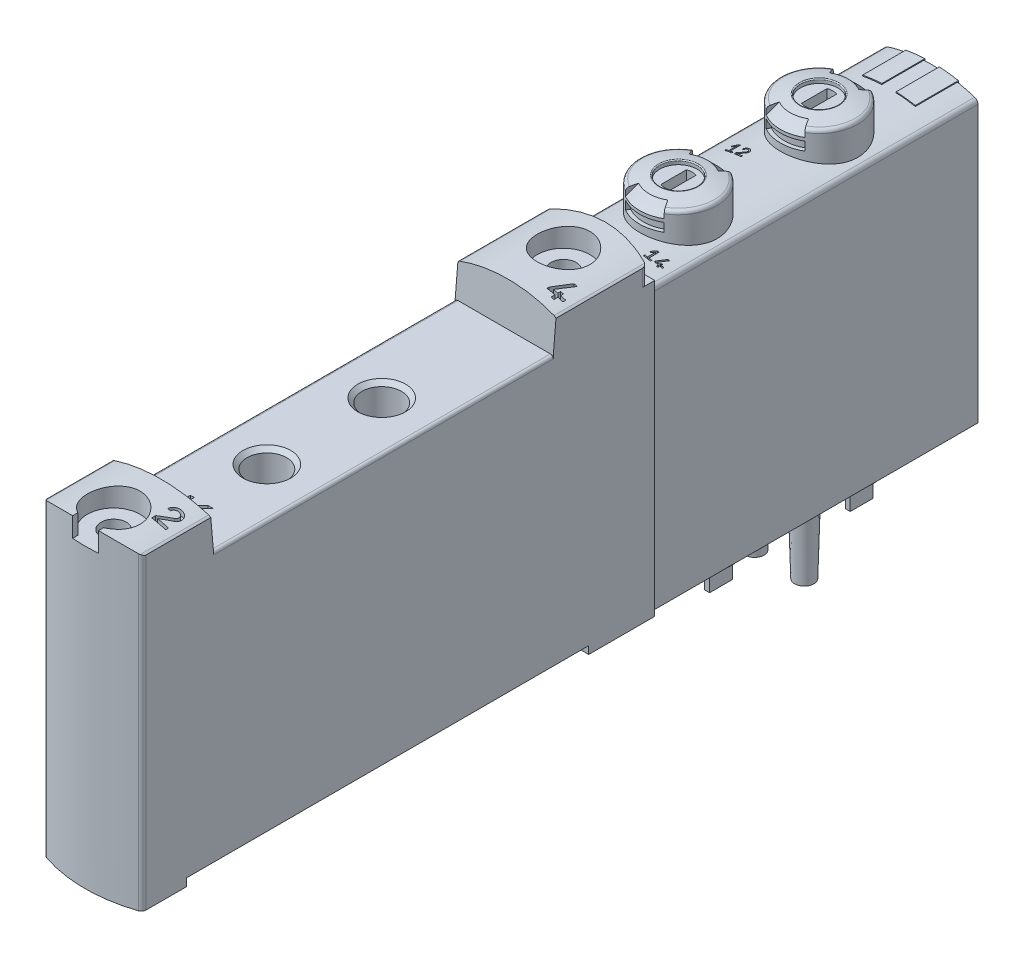
SolidWorks part; units mm, degrees
ref_plane "Front Plane" through (0, 0, 0) normal (0, 0, 1) x (1, 0, 0)
ref_plane "Top Plane" through (0, 0, 0) normal (0, 1, 0) x (1, 0, 0)
ref_plane "Right Plane" through (0, 0, 0) normal (1, 0, 0) x (0, 0, -1)
ref_plane "Plane1" through (0, 0, -23.2) normal (0, 0, 1) x (1, 0, 0)
sketch "Sketch1" plane through (0, 0, -23.2) normal (0, 0, 1) x (1, 0, 0)
  line L0 (-4.9, 29.2163) -> (-4.9, 0)
  line L1 (-4.9, 0) -> (4.9, 0)
  line L2 (4.9, 0) -> (4.9, 29.2163)
  arc A0 (4.9, 29.2163) -> (4.5517, 29.6927) centre (4.4, 29.2163) ccw
  arc A1 (4.5517, 29.6927) -> (-4.5517, 29.6927) centre (0, 15.4) ccw
  arc A2 (-4.5517, 29.6927) -> (-4.9, 29.2163) centre (-4.4, 29.2163) ccw
extrude "Boss-Extrude1" add sketch "Sketch1" along normal blind 34
ref_plane "Plane2" through (0, 0, 0) normal (1, 0, 0) x (0, 0, -1)
sketch "Sketch2" plane through (0, 0, 0) normal (1, 0, 0) x (0, 0, -1)
  line L0 (-10.88, 0.4) -> (-10.88, 0)
  line L1 (-10.88, 0) -> (23.22, 0)
  line L2 (23.22, 0) -> (23.22, 0.4)
  line L3 (23.22, 0.4) -> (-10.88, 0.4)
extrude "Cut-Extrude1" cut sketch "Sketch2" against normal blind 6 and the other way blind 6
ref_plane "Plane3" through (0, 0, 0) normal (0, 1, 0) x (1, 0, 0)
sketch "Sketch3" plane through (0, 0, 0) normal (0, 1, 0) x (1, 0, 0)
  line L0 (-3.15, 2.4653) -> (-3.15, -2.4653)
  line L1 (3.15, -2.4653) -> (3.15, 2.4653)
  arc A0 (-3.15, -2.4653) -> (3.15, -2.4653) centre (0, 0) ccw
  arc A1 (3.15, 2.4653) -> (-3.15, 2.4653) centre (0, 0) ccw
extrude "Cut-Extrude2" cut sketch "Sketch3" along normal blind 1.9
ref_plane "Plane4" through (0, 0, 0) normal (0, 1, 0) x (1, 0, 0)
sketch "Sketch4" plane through (0, 0, 0) normal (0, 1, 0) x (1, 0, 0)
  line L0 (-3.15, 17.1653) -> (-3.15, 12.2347)
  line L1 (3.15, 12.2347) -> (3.15, 17.1653)
  arc A0 (-3.15, 12.2347) -> (3.15, 12.2347) centre (0, 14.7) ccw
  arc A1 (3.15, 17.1653) -> (-3.15, 17.1653) centre (0, 14.7) ccw
extrude "Cut-Extrude3" cut sketch "Sketch4" along normal blind 1.9
ref_plane "Plane5" through (0, 0, 0) normal (1, 0, 0) x (0, 0, -1)
sketch "Sketch5" plane through (0, 0, 0) normal (1, 0, 0) x (0, 0, -1)
  line L0 (0, 2.1) -> (3.05, 2.1)
  line L1 (3.05, 2.1) -> (3.05, 1.1)
  line L2 (3.05, 1.1) -> (2.25, 1.1)
  line L3 (2.25, 1.1) -> (2.25, -1.4)
  line L4 (2.25, -1.4) -> (2.65, -1.4)
  line L5 (2.65, -1.4) -> (2.65, -1.72)
  line L6 (2.65, -1.72) -> (2.4306, -2.1)
  line L7 (2.4306, -2.1) -> (0, -2.1)
  line L8 (0, -2.1) -> (0, 2.1)
  line L9 (0, -2.1) -> (0, 2.1) construction
revolve "Revolve1" add sketch "Sketch5" angle 360 about L9 reverse direction yes
ref_plane "Plane6" through (0, 0, 0) normal (1, 0, 0) x (0, 0, -1)
sketch "Sketch6" plane through (0, 0, 0) normal (1, 0, 0) x (0, 0, -1)
  line L0 (14.7, 2.1) -> (17.75, 2.1)
  line L1 (17.75, 2.1) -> (17.75, 1.1)
  line L2 (17.75, 1.1) -> (16.95, 1.1)
  line L3 (16.95, 1.1) -> (16.95, -1.4)
  line L4 (16.95, -1.4) -> (17.35, -1.4)
  line L5 (17.35, -1.4) -> (17.35, -1.72)
  line L6 (17.35, -1.72) -> (17.1306, -2.1)
  line L7 (17.1306, -2.1) -> (14.7, -2.1)
  line L8 (14.7, -2.1) -> (14.7, 2.1)
  line L9 (14.7, -2.1) -> (14.7, 2.1) construction
revolve "Revolve2" add sketch "Sketch6" angle 360 about L9 reverse direction yes
ref_plane "Plane7" through (0, 0, -7.35) normal (0, 0, 1) x (1, 0, 0)
sketch "Sketch7" plane through (0, 0, -7.35) normal (0, 0, 1) x (1, 0, 0)
  line L0 (2.6, 0.4) -> (3.8, 0.4)
  line L1 (3.8, 0.4) -> (3.6, -6.9)
  line L2 (2.6, -7.0623) -> (2.6, 0.4)
  line L3 (2.6, -7.0623) -> (2.6, 0.4) construction
  arc A0 (3.6, -6.9) -> (2.6, -7.0623) centre (2.6, -3.9) cw
revolve "Revolve3" add sketch "Sketch7" angle 360 about L3 reverse direction yes
ref_plane "Plane8" through (0, 0, -7.35) normal (0, 0, 1) x (1, 0, 0)
sketch "Sketch8" plane through (0, 0, -7.35) normal (0, 0, 1) x (1, 0, 0)
  line L0 (-2.6, 0.4) -> (-1.4, 0.4)
  line L1 (-1.4, 0.4) -> (-1.6, -6.9)
  line L2 (-2.6, -7.0623) -> (-2.6, 0.4)
  line L3 (-2.6, -7.0623) -> (-2.6, 0.4) construction
  arc A0 (-1.6, -6.9) -> (-2.6, -7.0623) centre (-2.6, -3.9) cw
revolve "Revolve4" add sketch "Sketch8" angle 360 about L3 reverse direction yes
ref_plane "Plane9" through (0, -2.1, 0) normal (0, -1, 0) x (-1, 0, 0)
sketch "Sketch9" plane through (0, -2.1, 0) normal (0, -1, 0) x (-1, 0, 0)
  line L0 (-1.25, -1.2) -> (-0.75, -1.2)
  line L1 (-0.75, -1.2) -> (-0.75, 1.2)
  line L2 (-0.75, 1.2) -> (-1.25, 1.2)
  line L3 (-1.25, 1.2) -> (-1.25, -1.2)
extrude "Boss-Extrude2" add sketch "Sketch9" along normal blind 2.5
ref_plane "Plane10" through (0, -2.1, 0) normal (0, -1, 0) x (-1, 0, 0)
sketch "Sketch10" plane through (0, -2.1, 0) normal (0, -1, 0) x (-1, 0, 0)
  line L0 (0.75, -1.2) -> (1.25, -1.2)
  line L1 (1.25, -1.2) -> (1.25, 1.2)
  line L2 (1.25, 1.2) -> (0.75, 1.2)
  line L3 (0.75, 1.2) -> (0.75, -1.2)
extrude "Boss-Extrude3" add sketch "Sketch10" along normal blind 2.5
ref_plane "Plane11" through (0, -2.1, 0) normal (0, -1, 0) x (-1, 0, 0)
sketch "Sketch11" plane through (0, -2.1, 0) normal (0, -1, 0) x (-1, 0, 0)
  line L0 (-1.25, 13.5) -> (-0.75, 13.5)
  line L1 (-0.75, 13.5) -> (-0.75, 15.9)
  line L2 (-0.75, 15.9) -> (-1.25, 15.9)
  line L3 (-1.25, 15.9) -> (-1.25, 13.5)
extrude "Boss-Extrude4" add sketch "Sketch11" along normal blind 2.5
ref_plane "Plane12" through (0, -2.1, 0) normal (0, -1, 0) x (-1, 0, 0)
sketch "Sketch12" plane through (0, -2.1, 0) normal (0, -1, 0) x (-1, 0, 0)
  line L0 (0.75, 13.5) -> (1.25, 13.5)
  line L1 (1.25, 13.5) -> (1.25, 15.9)
  line L2 (1.25, 15.9) -> (0.75, 15.9)
  line L3 (0.75, 15.9) -> (0.75, 13.5)
extrude "Boss-Extrude5" add sketch "Sketch12" along normal blind 2.5
ref_plane "Plane13" through (0, 0, 0) normal (1, 0, 0) x (0, 0, -1)
sketch "Sketch13" plane through (0, 0, 0) normal (1, 0, 0) x (0, 0, -1)
  line L0 (-3.2, 33.13) -> (-1.25, 33.13)
  line L1 (-1.25, 33.13) -> (-1.25, 33.4583)
  line L2 (0.85, 32.8364) -> (0.85, 28.4)
  line L3 (0.85, 28.4) -> (-3.2, 28.4)
  line L4 (-3.2, 28.4) -> (-3.2, 33.13)
  line L5 (-3.2, 28.4) -> (-3.2, 33.7) construction
  arc A0 (-1.25, 33.4583) -> (-1.1362, 33.5574) centre (-1.15, 33.4583) cw
  arc A1 (-1.1362, 33.5574) -> (0.55, 33.2237) centre (-3.2, 18.7) cw
  arc A2 (0.55, 33.2237) -> (0.85, 32.8364) centre (0.45, 32.8364) cw
revolve "Revolve5" add sketch "Sketch13" angle 360 about L5 reverse direction yes
ref_plane "Plane14" through (0, 0, 0) normal (1, 0, 0) x (0, 0, -1)
sketch "Sketch14" plane through (0, 0, 0) normal (1, 0, 0) x (0, 0, -1)
  line L0 (11.5, 33.13) -> (13.45, 33.13)
  line L1 (13.45, 33.13) -> (13.45, 33.4583)
  line L2 (15.55, 32.8364) -> (15.55, 28.4)
  line L3 (15.55, 28.4) -> (11.5, 28.4)
  line L4 (11.5, 28.4) -> (11.5, 33.13)
  line L5 (11.5, 28.4) -> (11.5, 33.7) construction
  arc A0 (13.45, 33.4583) -> (13.5638, 33.5574) centre (13.55, 33.4583) cw
  arc A1 (13.5638, 33.5574) -> (15.25, 33.2237) centre (11.5, 18.7) cw
  arc A2 (15.25, 33.2237) -> (15.55, 32.8364) centre (15.15, 32.8364) cw
revolve "Revolve6" add sketch "Sketch14" angle 360 about L5 reverse direction yes
ref_plane "Plane15" through (0, 0, 0) normal (1, 0, 0) x (0, 0, -1)
sketch "Sketch15" plane through (0, 0, 0) normal (1, 0, 0) x (0, 0, -1)
  line L0 (-0.47, 33.7) -> (0.9, 32.33)
  line L1 (0.9, 32.33) -> (0.9, 32.05)
  line L2 (0.9, 32.05) -> (0.45, 32.05)
  line L3 (0.45, 32.05) -> (0.45, 31.15)
  line L4 (0.45, 31.15) -> (0.9, 31.15)
  line L5 (0.9, 31.15) -> (0.9, 30.5)
  line L6 (0.9, 30.5) -> (1.3, 30.5)
  line L7 (1.3, 30.5) -> (1.3, 33.7)
  line L8 (1.3, 33.7) -> (-0.47, 33.7)
  line L9 (-3.2, 30.5) -> (-3.2, 33.7) construction
revolve "Cut-Revolve1" cut sketch "Sketch15" angle 30 about L9 other way angle 30 reverse direction yes
ref_plane "Plane16" through (0, 0, 0) normal (1, 0, 0) x (0, 0, -1)
sketch "Sketch16" plane through (0, 0, 0) normal (1, 0, 0) x (0, 0, -1)
  line L0 (-7.7, 30.5) -> (-7.3, 30.5)
  line L1 (-7.3, 30.5) -> (-7.3, 31.15)
  line L2 (-7.3, 31.15) -> (-6.85, 31.15)
  line L3 (-6.85, 31.15) -> (-6.85, 32.05)
  line L4 (-6.85, 32.05) -> (-7.3, 32.05)
  line L5 (-7.3, 32.05) -> (-7.3, 32.33)
  line L6 (-7.3, 32.33) -> (-5.93, 33.7)
  line L7 (-5.93, 33.7) -> (-7.7, 33.7)
  line L8 (-7.7, 33.7) -> (-7.7, 30.5)
  line L9 (-3.2, 33.7) -> (-3.2, 30.5) construction
revolve "Cut-Revolve2" cut sketch "Sketch16" angle 30 about L9 other way angle 30 reverse direction yes
ref_plane "Plane17" through (0, 33.13, 0) normal (0, 1, 0) x (1, 0, 0)
sketch "Sketch17" plane through (0, 33.13, 0) normal (0, 1, 0) x (1, 0, 0)
  line L0 (0.5, -4.5344) -> (0.5, -1.8656)
  line L1 (-0.5, -1.8656) -> (-0.5, -4.5344)
  arc A0 (-0.5, -4.5344) -> (0.5, -4.5344) centre (0, -3.2) ccw
  arc A1 (0.5, -1.8656) -> (-0.5, -1.8656) centre (0, -3.2) ccw
extrude "Cut-Extrude4" cut sketch "Sketch17" against normal blind 1.7
ref_plane "Plane18" through (0, 0, 0) normal (1, 0, 0) x (0, 0, -1)
sketch "Sketch18" plane through (0, 0, 0) normal (1, 0, 0) x (0, 0, -1)
  line L0 (14.23, 33.7) -> (15.6, 32.33)
  line L1 (15.6, 32.33) -> (15.6, 32.05)
  line L2 (15.6, 32.05) -> (15.15, 32.05)
  line L3 (15.15, 32.05) -> (15.15, 31.15)
  line L4 (15.15, 31.15) -> (15.6, 31.15)
  line L5 (15.6, 31.15) -> (15.6, 30.5)
  line L6 (15.6, 30.5) -> (16, 30.5)
  line L7 (16, 30.5) -> (16, 33.7)
  line L8 (16, 33.7) -> (14.23, 33.7)
  line L9 (11.5, 30.5) -> (11.5, 33.7) construction
revolve "Cut-Revolve3" cut sketch "Sketch18" angle 30 about L9 other way angle 30 reverse direction yes
ref_plane "Plane19" through (0, 0, 0) normal (1, 0, 0) x (0, 0, -1)
sketch "Sketch19" plane through (0, 0, 0) normal (1, 0, 0) x (0, 0, -1)
  line L0 (7, 30.5) -> (7.4, 30.5)
  line L1 (7.4, 30.5) -> (7.4, 31.15)
  line L2 (7.4, 31.15) -> (7.85, 31.15)
  line L3 (7.85, 31.15) -> (7.85, 32.05)
  line L4 (7.85, 32.05) -> (7.4, 32.05)
  line L5 (7.4, 32.05) -> (7.4, 32.33)
  line L6 (7.4, 32.33) -> (8.77, 33.7)
  line L7 (8.77, 33.7) -> (7, 33.7)
  line L8 (7, 33.7) -> (7, 30.5)
  line L9 (11.5, 33.7) -> (11.5, 30.5) construction
revolve "Cut-Revolve4" cut sketch "Sketch19" angle 30 about L9 other way angle 30 reverse direction yes
ref_plane "Plane20" through (0, 33.13, 0) normal (0, 1, 0) x (1, 0, 0)
sketch "Sketch20" plane through (0, 33.13, 0) normal (0, 1, 0) x (1, 0, 0)
  line L0 (0.5, 10.1656) -> (0.5, 12.8344)
  line L1 (-0.5, 12.8344) -> (-0.5, 10.1656)
  arc A0 (-0.5, 10.1656) -> (0.5, 10.1656) centre (0, 11.5) ccw
  arc A1 (0.5, 12.8344) -> (-0.5, 12.8344) centre (0, 11.5) ccw
extrude "Cut-Extrude5" cut sketch "Sketch20" against normal blind 1.7
ref_plane "Plane21" through (0, 0, -23.3) normal (0, 0, 1) x (1, 0, 0)
sketch "Sketch21" plane through (0, 0, -23.3) normal (0, 0, 1) x (1, 0, 0)
  line L0 (0.75, 30.4814) -> (0.75, 27)
  line L1 (0.75, 27) -> (2.75, 27)
  line L2 (2.75, 27) -> (2.75, 30.2475)
  arc A0 (2.75, 30.2475) -> (0.75, 30.4814) centre (0, 15.4) ccw
extrude "Boss-Extrude6" add sketch "Sketch21" along normal blind 4.5
ref_plane "Plane22" through (0, 0, -23.3) normal (0, 0, 1) x (1, 0, 0)
sketch "Sketch22" plane through (0, 0, -23.3) normal (0, 0, 1) x (1, 0, 0)
  line L0 (-2.75, 30.2475) -> (-2.75, 27)
  line L1 (-2.75, 27) -> (-0.75, 27)
  line L2 (-0.75, 27) -> (-0.75, 30.4814)
  arc A0 (-0.75, 30.4814) -> (-2.75, 30.2475) centre (0, 15.4) ccw
extrude "Boss-Extrude7" add sketch "Sketch22" along normal blind 4.5
ref_plane "Plane23" through (0, 0, 0) normal (0, 1, 0) x (1, 0, 0)
sketch "Sketch23" plane through (0, 0, 0) normal (0, 1, 0) x (1, 0, 0)
  line L0 (5.125, -63.9426) -> (5.125, -10.8)
  line L1 (5.125, -10.8) -> (-5.125, -10.8)
  line L2 (-5.125, -10.8) -> (-5.125, -63.9426)
  arc A0 (-5.125, -63.9426) -> (-4.7845, -64.4165) centre (-4.625, -63.9426) ccw
  arc A1 (-4.7845, -64.4165) -> (4.7845, -64.4165) centre (0, -50.2) ccw
  arc A2 (4.7845, -64.4165) -> (5.125, -63.9426) centre (4.625, -63.9426) ccw
extrude "Boss-Extrude8" add sketch "Sketch23" along normal blind 33.1
ref_plane "Plane24" through (0, 0, 0) normal (1, 0, 0) x (0, 0, -1)
sketch "Sketch24" plane through (0, 0, 0) normal (1, 0, 0) x (0, 0, -1)
  line L0 (-57.7749, 38.9) -> (-56.9, 28.9)
  line L1 (-56.9, 28.9) -> (-21.4, 28.9)
  line L2 (-21.4, 28.9) -> (-20.5251, 38.9)
  line L3 (-20.5251, 38.9) -> (-57.7749, 38.9)
extrude "Cut-Extrude6" cut sketch "Sketch24" against normal blind 10 and the other way blind 10
ref_plane "Plane25" through (0, 30.4, 0) normal (0, 1, 0) x (1, 0, 0)
sketch "Sketch25" plane through (0, 30.4, 0) normal (0, 1, 0) x (1, 0, 0)
  line L0 (-5.125, -8.8) -> (-5.125, -12.0574)
  line L1 (5.125, -12.0574) -> (5.125, -8.8)
  line L2 (5.125, -8.8) -> (-5.125, -8.8)
  arc A0 (-5.125, -12.0574) -> (-4.7845, -11.5835) centre (-4.625, -12.0574) cw
  arc A1 (-4.7845, -11.5835) -> (4.7845, -11.5835) centre (0, -25.8) cw
  arc A2 (4.7845, -11.5835) -> (5.125, -12.0574) centre (4.625, -12.0574) cw
extrude "Cut-Extrude7" cut sketch "Sketch25" along normal blind 10
ref_plane "Plane26" through (0, 0, 0) normal (1, 0, 0) x (0, 0, -1)
sketch "Sketch26" plane through (0, 0, 0) normal (1, 0, 0) x (0, 0, -1)
  line L0 (-59.7, -0.2) -> (-17.7, -0.2)
  line L1 (-17.7, -0.2) -> (-17.7, 0.8)
  line L2 (-17.7, 0.8) -> (-59.7, 0.8)
  line L3 (-59.7, 0.8) -> (-59.7, -0.2)
extrude "Cut-Extrude8" cut sketch "Sketch26" against normal blind 10 and the other way blind 10
ref_plane "Plane27" through (0, 0, 10.8) normal (0, 0, 1) x (1, 0, 0)
sketch "Sketch27" plane through (0, 0, 10.8) normal (0, 0, 1) x (1, 0, 0)
  line L0 (-5.25, 35.1) -> (-5.25, 31.7999)
  line L1 (5.25, 31.7999) -> (5.25, 35.1)
  line L2 (5.25, 35.1) -> (-5.25, 35.1)
  arc A0 (-5.25, 31.7999) -> (-4.9138, 32.2723) centre (-4.75, 31.7999) cw
  arc A1 (-4.9138, 32.2723) -> (4.9138, 32.2723) centre (0, 18.1) cw
  arc A2 (4.9138, 32.2723) -> (5.25, 31.7999) centre (4.75, 31.7999) cw
extrude "Cut-Extrude9" cut sketch "Sketch27" along normal blind 55
ref_plane "Plane28" through (0, 0, 21.4) normal (0, 0, 1) x (1, 0, 0)
sketch "Sketch28" plane through (0, 0, 21.4) normal (0, 0, 1) x (1, 0, 0)
  line L0 (-4.825, 28.9) -> (4.825, 28.9)
  line L1 (5.125, 28.6) -> (5.125, 33.6)
  line L2 (5.125, 33.6) -> (-5.125, 33.6)
  line L3 (-5.125, 33.6) -> (-5.125, 28.6)
  arc A0 (-5.125, 28.6) -> (-4.825, 28.9) centre (-4.825, 28.6) cw
  arc A1 (4.825, 28.9) -> (5.125, 28.6) centre (4.825, 28.6) cw
extrude "Cut-Extrude10" cut sketch "Sketch28" along normal blind 35.5
ref_plane "Plane29" through (0, 33.1, 0) normal (0, 1, 0) x (1, 0, 0)
sketch "Sketch29" plane through (0, 33.1, 0) normal (0, 1, 0) x (1, 0, 0)
  line L0 (-1.35, -64.5958) -> (-1.35, -66)
  line L1 (-1.35, -66) -> (1.35, -66)
  line L2 (1.35, -66) -> (1.35, -64.5958)
  arc A0 (1.35, -64.5958) -> (-1.35, -64.5958) centre (0, -62.2) ccw
extrude "Cut-Extrude11" cut sketch "Sketch29" against normal blind 2.1 and the other way blind 2.1
ref_plane "Plane30" through (0, 0, 0) normal (1, 0, 0) x (0, 0, -1)
sketch "Sketch30" plane through (0, 0, 0) normal (1, 0, 0) x (0, 0, -1)
  line L0 (-62.2, 31) -> (-60.875, 31)
  line L1 (-60.875, 31) -> (-60.875, 0)
  line L2 (-60.875, 0) -> (-62.2, 0)
  line L3 (-62.2, 0) -> (-62.2, 31)
  line L4 (-62.2, 0) -> (-62.2, 31) construction
revolve "Cut-Revolve5" cut sketch "Sketch30" angle 360 about L4 reverse direction yes
ref_plane "Plane31" through (0, 0, 0) normal (1, 0, 0) x (0, 0, -1)
sketch "Sketch31" plane through (0, 0, 0) normal (1, 0, 0) x (0, 0, -1)
  line L0 (-15.2, 33.2) -> (-12.45, 33.2)
  line L1 (-12.45, 33.2) -> (-12.45, 31)
  line L2 (-12.45, 31) -> (-13.875, 31)
  line L3 (-13.875, 31) -> (-13.875, 0)
  line L4 (-13.875, 0) -> (-15.2, 0)
  line L5 (-15.2, 0) -> (-15.2, 33.2)
  line L6 (-15.2, 0) -> (-15.2, 33.2) construction
revolve "Cut-Revolve6" cut sketch "Sketch31" angle 360 about L6 reverse direction yes
ref_plane "Plane32" through (0, 0, 0) normal (1, 0, 0) x (0, 0, -1)
sketch "Sketch32" plane through (0, 0, 0) normal (1, 0, 0) x (0, 0, -1)
  line L0 (-34.2, 28.9) -> (-31.7, 28.9)
  line L1 (-31.7, 28.9) -> (-32.133, 28.467)
  line L2 (-32.133, 28.467) -> (-32.133, 22.3)
  line L3 (-32.133, 22.3) -> (-34.2, 22.3)
  line L4 (-34.2, 22.3) -> (-34.2, 28.9)
  line L5 (-34.2, 22.3) -> (-34.2, 28.9) construction
revolve "Cut-Revolve7" cut sketch "Sketch32" angle 360 about L5 reverse direction yes
cosmetic thread "Cosmetic Thread1" parameters "D1"=4.5, "D2"=5
ref_plane "Plane33" through (0, 0, 0) normal (1, 0, 0) x (0, 0, -1)
sketch "Sketch33" plane through (0, 0, 0) normal (1, 0, 0) x (0, 0, -1)
  line L0 (-46.2, 28.9) -> (-43.7, 28.9)
  line L1 (-43.7, 28.9) -> (-44.133, 28.467)
  line L2 (-44.133, 28.467) -> (-44.133, 22.3)
  line L3 (-44.133, 22.3) -> (-46.2, 22.3)
  line L4 (-46.2, 22.3) -> (-46.2, 28.9)
  line L5 (-46.2, 22.3) -> (-46.2, 28.9) construction
revolve "Cut-Revolve8" cut sketch "Sketch33" angle 360 about L5 reverse direction yes
cosmetic thread "Cosmetic Thread2" parameters "D1"=4.5, "D2"=5
ref_plane "Plane34" through (0, 0, 0) normal (1, 0, 0) x (0, 0, -1)
sketch "Sketch34" plane through (0, 0, 0) normal (1, 0, 0) x (0, 0, -1)
  line L0 (-29.2, 7.3) -> (-27.1, 7.3)
  line L1 (-27.1, 7.3) -> (-27.1, 2.8)
  line L2 (-27.1, 2.8) -> (-26.2, 2.8)
  line L3 (-26.2, 2.8) -> (-26.2, 1.3)
  line L4 (-26.2, 1.3) -> (-25.7, 0.8)
  line L5 (-25.7, 0.8) -> (-29.2, 0.8)
  line L6 (-29.2, 0.8) -> (-29.2, 7.3)
  line L7 (-29.2, 0.8) -> (-29.2, 7.3) construction
revolve "Cut-Revolve9" cut sketch "Sketch34" angle 360 about L7 reverse direction yes
ref_plane "Plane35" through (0, 0, 0) normal (1, 0, 0) x (0, 0, -1)
sketch "Sketch35" plane through (0, 0, 0) normal (1, 0, 0) x (0, 0, -1)
  line L0 (-40.2, 7.3) -> (-38.1, 7.3)
  line L1 (-38.1, 7.3) -> (-38.1, 2.8)
  line L2 (-38.1, 2.8) -> (-37.2, 2.8)
  line L3 (-37.2, 2.8) -> (-37.2, 1.3)
  line L4 (-37.2, 1.3) -> (-36.7, 0.8)
  line L5 (-36.7, 0.8) -> (-40.2, 0.8)
  line L6 (-40.2, 0.8) -> (-40.2, 7.3)
  line L7 (-40.2, 0.8) -> (-40.2, 7.3) construction
revolve "Cut-Revolve10" cut sketch "Sketch35" angle 360 about L7 reverse direction yes
ref_plane "Plane36" through (0, 0, 0) normal (1, 0, 0) x (0, 0, -1)
sketch "Sketch36" plane through (0, 0, 0) normal (1, 0, 0) x (0, 0, -1)
  line L0 (-51.2, 7.3) -> (-49.1, 7.3)
  line L1 (-49.1, 7.3) -> (-49.1, 2.8)
  line L2 (-49.1, 2.8) -> (-48.2, 2.8)
  line L3 (-48.2, 2.8) -> (-48.2, 1.3)
  line L4 (-48.2, 1.3) -> (-47.7, 0.8)
  line L5 (-47.7, 0.8) -> (-51.2, 0.8)
  line L6 (-51.2, 0.8) -> (-51.2, 7.3)
  line L7 (-51.2, 0.8) -> (-51.2, 7.3) construction
revolve "Cut-Revolve11" cut sketch "Sketch36" angle 360 about L7 reverse direction yes
ref_plane "Plane37" through (0, 33.1, 0) normal (0, 1, 0) x (1, 0, 0)
sketch "Sketch37" plane through (0, 33.1, 0) normal (0, 1, 0) x (1, 0, 0)
  line L0 (-3.3985, 5.738) -> (-3.2978, 5.6676)
  line L1 (-3.2978, 5.6676) -> (-3.075, 5.9858)
  line L2 (-3.075, 5.9858) -> (-3.075, 5.15)
  line L3 (-3.075, 5.15) -> (-3.375, 5.15)
  line L4 (-3.375, 5.15) -> (-3.375, 5)
  line L5 (-3.375, 5) -> (-2.625, 5)
  line L6 (-2.625, 5) -> (-2.625, 5.15)
  line L7 (-2.625, 5.15) -> (-2.925, 5.15)
  line L8 (-2.925, 5.15) -> (-2.925, 6.2)
  line L9 (-2.925, 6.2) -> (-3.075, 6.2)
  line L10 (-3.075, 6.2) -> (-3.3985, 5.738)
extrude "Cut-Extrude12" cut sketch "Sketch37" against normal blind 3.5 and the other way blind 3.5
ref_plane "Plane38" through (0, 33.1, 0) normal (0, 1, 0) x (1, 0, 0)
sketch "Sketch38" plane through (0, 33.1, 0) normal (0, 1, 0) x (1, 0, 0)
  line L0 (-2.3625, 5.8375) -> (-2.2125, 5.8375)
  line L1 (-1.8546, 5.6826) -> (-2.3625, 5.2057)
  line L2 (-2.3625, 5.2057) -> (-2.3625, 5)
  line L3 (-2.3625, 5) -> (-1.6375, 5)
  line L4 (-1.6375, 5) -> (-1.6375, 5.15)
  line L5 (-1.6375, 5.15) -> (-2.2027, 5.15)
  line L6 (-2.2027, 5.15) -> (-1.7519, 5.5732)
  arc A0 (-2.2125, 5.8375) -> (-1.8546, 5.6826) centre (-2, 5.8375) cw
  arc A1 (-1.7519, 5.5732) -> (-2.3625, 5.8375) centre (-2, 5.8375) ccw
extrude "Cut-Extrude13" cut sketch "Sketch38" against normal blind 3.5 and the other way blind 3.5
ref_plane "Plane39" through (0, 33.1, 0) normal (0, 1, 0) x (1, 0, 0)
sketch "Sketch39" plane through (0, 33.1, 0) normal (0, 1, 0) x (1, 0, 0)
  line L0 (2.1015, -8.262) -> (2.2022, -8.3324)
  line L1 (2.2022, -8.3324) -> (2.425, -8.0142)
  line L2 (2.425, -8.0142) -> (2.425, -8.85)
  line L3 (2.425, -8.85) -> (2.125, -8.85)
  line L4 (2.125, -8.85) -> (2.125, -9)
  line L5 (2.125, -9) -> (2.875, -9)
  line L6 (2.875, -9) -> (2.875, -8.85)
  line L7 (2.875, -8.85) -> (2.575, -8.85)
  line L8 (2.575, -8.85) -> (2.575, -7.8)
  line L9 (2.575, -7.8) -> (2.425, -7.8)
  line L10 (2.425, -7.8) -> (2.1015, -8.262)
extrude "Cut-Extrude14" cut sketch "Sketch39" against normal blind 3.5 and the other way blind 3.5
ref_plane "Plane40" through (0, 33.1, 0) normal (0, 1, 0) x (1, 0, 0)
sketch "Sketch40" plane through (0, 33.1, 0) normal (0, 1, 0) x (1, 0, 0)
  line L0 (3.085, -8.8) -> (3.5, -8.8)
  line L1 (3.5, -8.8) -> (3.5, -9)
  line L2 (3.5, -9) -> (3.65, -9)
  line L3 (3.65, -9) -> (3.65, -8.8)
  line L4 (3.65, -8.8) -> (3.915, -8.8)
  line L5 (3.915, -8.8) -> (3.915, -8.65)
  line L6 (3.915, -8.65) -> (3.65, -8.65)
  line L7 (3.65, -8.65) -> (3.65, -8.5)
  line L8 (3.65, -8.5) -> (3.5, -8.5)
  line L9 (3.5, -8.5) -> (3.5, -8.65)
  line L10 (3.5, -8.65) -> (3.2699, -8.65)
  line L11 (3.2699, -8.65) -> (3.6663, -7.8)
  line L12 (3.6663, -7.8) -> (3.5008, -7.8)
  line L13 (3.5008, -7.8) -> (3.085, -8.6917)
  line L14 (3.085, -8.6917) -> (3.085, -8.8)
extrude "Cut-Extrude15" cut sketch "Sketch40" against normal blind 3.5 and the other way blind 3.5
ref_plane "Plane41" through (0, 33.1, 0) normal (0, 1, 0) x (1, 0, 0)
sketch "Sketch41" plane through (0, 33.1, 0) normal (0, 1, 0) x (1, 0, 0)
  line L0 (2.67, -19.6) -> (3.5, -19.6)
  line L1 (3.5, -19.6) -> (3.5, -20)
  line L2 (3.5, -20) -> (3.8, -20)
  line L3 (3.8, -20) -> (3.8, -19.6)
  line L4 (3.8, -19.6) -> (4.33, -19.6)
  line L5 (4.33, -19.6) -> (4.33, -19.3)
  line L6 (4.33, -19.3) -> (3.8, -19.3)
  line L7 (3.8, -19.3) -> (3.8, -19)
  line L8 (3.8, -19) -> (3.5, -19)
  line L9 (3.5, -19) -> (3.5, -19.3)
  line L10 (3.5, -19.3) -> (3.0399, -19.3)
  line L11 (3.0399, -19.3) -> (3.8326, -17.6)
  line L12 (3.8326, -17.6) -> (3.5016, -17.6)
  line L13 (3.5016, -17.6) -> (2.67, -19.3834)
  line L14 (2.67, -19.3834) -> (2.67, -19.6)
extrude "Cut-Extrude16" cut sketch "Sketch41" against normal blind 1 and the other way blind 1
ref_plane "Plane42" through (0, 33.1, 0) normal (0, 1, 0) x (1, 0, 0)
sketch "Sketch42" plane through (0, 33.1, 0) normal (0, 1, 0) x (1, 0, 0)
  line L0 (2.775, -59.325) -> (3.075, -59.325)
  line L1 (3.7909, -59.6349) -> (2.775, -60.5885)
  line L2 (2.775, -60.5885) -> (2.775, -61)
  line L3 (2.775, -61) -> (4.225, -61)
  line L4 (4.225, -61) -> (4.225, -60.7)
  line L5 (4.225, -60.7) -> (3.0946, -60.7)
  line L6 (3.0946, -60.7) -> (3.9962, -59.8536)
  arc A0 (3.075, -59.325) -> (3.7909, -59.6349) centre (3.5, -59.325) cw
  arc A1 (3.9962, -59.8536) -> (2.775, -59.325) centre (3.5, -59.325) ccw
extrude "Cut-Extrude17" cut sketch "Sketch42" against normal blind 1 and the other way blind 1
ref_plane "Plane43" through (0, 33.1, 0) normal (0, 1, 0) x (1, 0, 0)
sketch "Sketch43" plane through (0, 33.1, 0) normal (0, 1, 0) x (1, 0, 0)
  line L0 (-1.2, -53) -> (-1.2, -56)
  line L1 (-1.2, -56) -> (-0.78, -56)
  line L2 (-0.78, -56) -> (-0.78, -54.95)
  line L3 (-0.78, -54.95) -> (-0.3273, -54.5041)
  line L4 (-0.3273, -54.5041) -> (0.66, -56)
  line L5 (0.66, -56) -> (1.2, -56)
  line L6 (1.2, -56) -> (0, -54.1818)
  line L7 (0, -54.1818) -> (1.2, -53)
  line L8 (1.2, -53) -> (0.66, -53)
  line L9 (0.66, -53) -> (-0.78, -54.4182)
  line L10 (-0.78, -54.4182) -> (-0.78, -53)
  line L11 (-0.78, -53) -> (-1.2, -53)
extrude "Cut-Extrude18" cut sketch "Sketch43" against normal blind 4.5 and the other way blind 4.5
